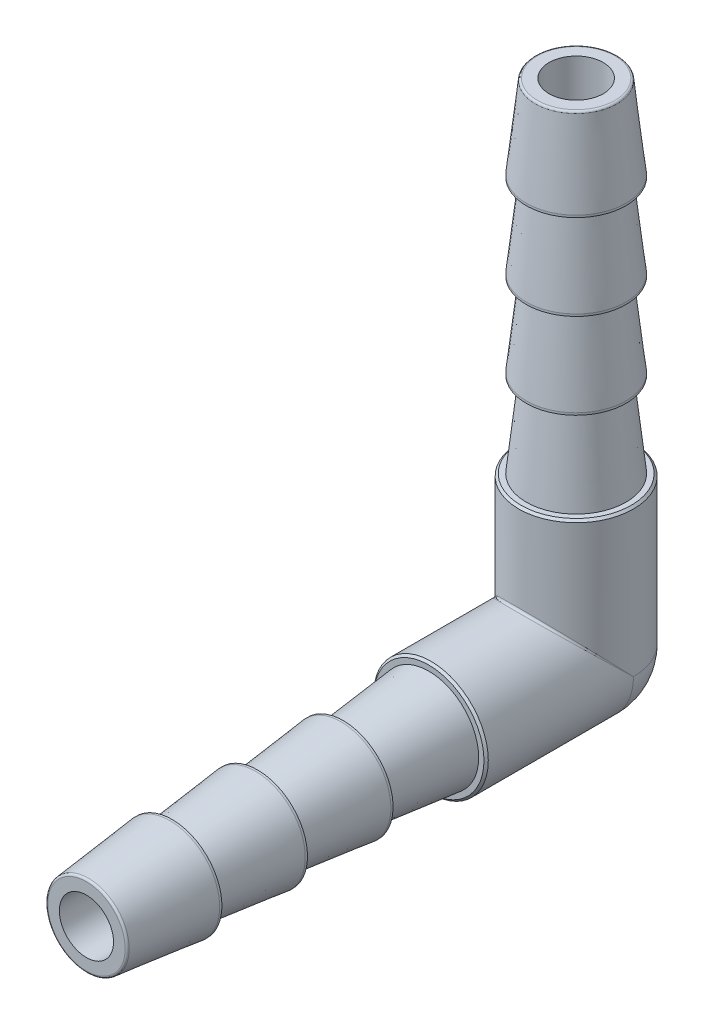
SolidWorks part; units mm, degrees
note: '?' marks a value the reader was unsure of.
ref_plane "Front Plane" through (0, 0, 0) normal (0, 0, 1) x (1, 0, 0)
ref_plane "Top Plane" through (0, 0, 0) normal (0, 1, 0) x (1, 0, 0)
ref_plane "Right Plane" through (0, 0, 0) normal (1, 0, 0) x (0, 0, -1)
sketch "Sketch1" plane through (0, 0, 0) normal (1, 0, 0) x (0, 0, -1)
  line L0 (-28.702, 0) -> (0, 0) construction
  line L2 (-1.5875, 28.702) -> (1.5875, 28.702) construction
  line L3 (-28.702, 2.3813) -> (-28.702, -2.3813) construction
  line L5 (0, 3.3592) -> (0, -3.3592) construction
  line L6 (-28.702, 1.5875) -> (-28.702, -1.5875) construction
  line L7 (-28.702, 2.921) -> (-28.702, -2.921) construction
  line L8 (-2.3813, 28.702) -> (2.3813, 28.702) construction
  line L11 (-8.636, 3.3592) -> (-8.636, -3.3592) construction
  line L12 (-3.3592, 8.636) -> (3.3592, 8.636) construction
  line L13 (3.3592, 8.636) -> (3.3592, -3.3592) construction
  line L14 (0, 0) -> (0, 28.702) construction
  line L15 (-8.636, -3.3592) -> (3.3592, -3.3592) construction
  point P1 (-8.636, 0)
  point P32 (0, 8.636)
  dimension "ID" = 3.175
  dimension "Barb End Length" = 20.066
  dimension "Barb End Length2" = 20.066
  dimension "D2" = 6.7183
  dimension "Length" = 28.702
  dimension "For Hose ID" = 4.7625
  dimension "Barb OD" = 5.842
sketch "Sketch2" plane through (0, 0, 0) normal (1, 0, 0) x (0, 0, -1)
  line L1 (-28.702, 0) -> (-28.702, 3.3592)
  line L2 (0, 0) -> (0, 3.3592) construction
  line L3 (-28.702, 3.3592) -> (0, 3.3592)
  line L4 (0, 3.3592) -> (0, -3.3592) construction
  line L9 (-28.702, 0) -> (0, 0) construction
  line L12 (3.3592, 0) -> (-28.702, 0)
  arc A0 (3.3592, 0) -> (0, 3.3592) centre (0, 0) ccw
revolve "Revolve1" add sketch "Sketch2" angle 360 about L9
sketch "Sketch3" plane through (0, 0, 0) normal (1, 0, 0) x (0, 0, -1)
  line L0 (-28.702, 3.3592) -> (-28.702, 2.3813)
  line L1 (-28.702, 3.3592) -> (-8.636, 3.3592)
  line L2 (-28.702, 2.3813) -> (-13.6525, 2.3813)
  line L3 (-28.702, 0) -> (0, 0) construction
  line L5 (-8.636, 3.3592) -> (-8.636, -3.3592) construction
  line L6 (-8.636, 2.921) -> (-13.6525, 2.3813)
  line L12 (-8.636, 2.921) -> (-8.636, 3.3592)
  dimension "D1" = 5.0165
revolve "Cut-Revolve1" cut sketch "Sketch3" angle 360 about L3
sketch "Sketch4" plane through (0, 0, 0) normal (1, 0, 0) x (0, 0, -1)
  line L0 (-8.636, 0) -> (-28.702, 0) construction
  line L1 (-28.702, 2.3813) -> (-28.702, -2.3813) construction
  line L2 (-23.6855, 2.921) -> (-23.8125, 2.921)
  line L4 (-23.6855, 2.3813) -> (-23.6855, 2.921)
  line L5 (-23.8125, 2.921) -> (-28.702, 2.3813)
  line L7 (-23.6855, 2.3813) -> (-28.702, 2.3813)
  dimension "D2" = 5.0165
revolve "Revolve2" add sketch "Sketch4" angle 360 about L0
pattern_linear "LPattern1" count 3 spacing 5.0165 along (0, 0, -1) of "Revolve2"
chamfer "Chamfer1" distance 0.127 angle 45 1 edges at (3.3592, 0, 8.636)
ref_axis "Axis1" through (-6.6672, 0, 0) along (1, 0, 0)
pattern_circular "CirPattern1" count 2 over 90 about axis through (-6.6672, 0, 0) along (1, 0, 0) of "Revolve1", "Cut-Revolve1", "Revolve2", "LPattern1", "Chamfer1"
sketch "Sketch5" plane through (0, 0, 0) normal (1, 0, 0) x (0, 0, -1)
  line L0 (0, 3.3592) -> (0, -3.3592) construction
  line L1 (-28.702, 1.5875) -> (0, 1.5875)
  line L2 (-28.702, 1.5875) -> (-28.702, 0)
  line L3 (-28.702, 0) -> (1.5875, 0)
  arc A0 (1.5875, 0) -> (0, 1.5875) centre (0, 0) ccw
revolve "Cut-Revolve2" cut sketch "Sketch5" angle 360 about L3
pattern_circular "CirPattern2" count 2 every 90 about axis through (-6.6672, 0, 0) along (1, 0, 0) of "Cut-Revolve2"
fillet "Fillet2" radius 0.127 3 edges at (0, 3.3592, 3.3591) (-2.3813, 28.702, 0) (-2.3813, 0, 28.702)
ref_axis "Axis2" through (0, 0, 0) along (0, 1, 0)?
ref_axis "Axis3" through (0, 0, 0) along (0, 0, 1)?
ref_point "Point1"
ref_point "Point2"
equation "\"Barb End Length2@Sketch1\" = \"Barb End Length@Sketch1\""
equation "\"D2@Sketch4\" = \"Barb End Length@Sketch1\" /  ( \"No. of Barbs@LPattern1\" + 1 ) "
equation "\"D1@Sketch3\"=\"D2@Sketch4\""
equation "\"D3@LPattern1\" = \"D2@Sketch4\""
equation "\"D2@Sketch1\"=\"Barb OD@Sketch1\"*1.15"
